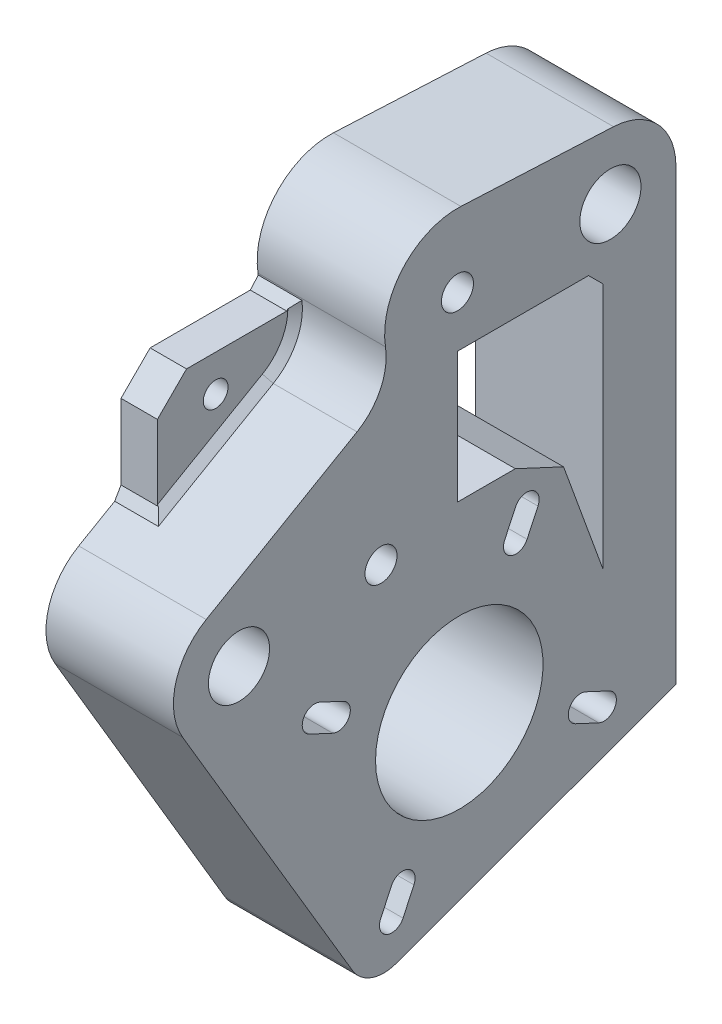
SolidWorks part; units mm, degrees
ref_plane "Front Plane" through (0, 0, 0) normal (0, 0, 1) x (1, 0, 0)
ref_plane "Top Plane" through (0, 0, 0) normal (0, 1, 0) x (1, 0, 0)
ref_plane "Right Plane" through (0, 0, 0) normal (1, 0, 0) x (0, 0, -1)
ref_plane "Plane1" through (0, 0, 0) normal (-1, 0, 0) x (0, -1, 0)
sketch "Sketch1" plane through (0, 0, 0) normal (-1, 0, 0) x (0, -1, 0)
  line L0 (11.2005, 72.3805) -> (-8.7575, 37.8123)
  line L1 (-24.9887, 29.5238) -> (-23.5812, 0)
  line L2 (-23.5812, 0) -> (46.6053, 0)
  line L3 (46.6053, 0) -> (62.0013, 42.3)
  line L4 (62.0013, 42.3) -> (11.2005, 72.3805)
  arc A0 (-8.7575, 37.8123) -> (-24.9887, 29.5238) centre (-15, 30) ccw
extrude "Boss-Extrude1" add sketch "Sketch1" against normal blind 17.5
sketch "Sketch2" plane through (0, 0, 0) normal (-1, 0, 0) x (0, -1, 0)
  line L0 (-8.7575, 37.8123) -> (3.302, 58.7)
  line L1 (3.302, 58.7) -> (-12, 58.7)
  line L2 (-12, 58.7) -> (-12, 39.5394)
  arc A0 (-12, 39.5394) -> (-8.7575, 37.8123) centre (-15, 30) cw
extrude "Boss-Extrude2" add sketch "Sketch2" against normal blind 5
sketch "Sketch3" plane through (0, 0, 0) normal (-1, 0, 0) x (0, 0, 1)
  line L0 (18.9442, -15.9372) -> (20.4384, -19.1415)
  line L1 (23.5198, -17.7046) -> (22.0256, -14.5003)
  arc A0 (20.4384, -19.1415) -> (23.5198, -17.7046) centre (21.9791, -18.423) ccw
  arc A1 (22.0256, -14.5003) -> (18.9442, -15.9372) centre (20.4849, -15.2188) ccw
extrude "Cut-Extrude1" cut sketch "Sketch3" against normal through all
sketch "Sketch4" plane through (0, 0, 0) normal (-1, 0, 0) x (0, 0, 1)
  line L0 (48.8969, -24.2807) -> (45.6927, -25.7748)
  line L1 (47.1296, -28.8563) -> (50.3338, -27.3621)
  arc A0 (50.3338, -27.3621) -> (48.8969, -24.2807) centre (49.6154, -25.8214) ccw
  arc A1 (45.6927, -25.7748) -> (47.1296, -28.8563) centre (46.4111, -27.3156) ccw
extrude "Cut-Extrude2" cut sketch "Sketch4" against normal through all
sketch "Sketch5" plane through (0, 0, 0) normal (-1, 0, 0) x (0, 0, 1)
  line L0 (35.9779, -52.466) -> (37.472, -55.6703)
  line L1 (40.5535, -54.2334) -> (39.0593, -51.0291)
  arc A0 (37.472, -55.6703) -> (40.5535, -54.2334) centre (39.0128, -54.9518) ccw
  arc A1 (39.0593, -51.0291) -> (35.9779, -52.466) centre (37.5186, -51.7476) ccw
extrude "Cut-Extrude3" cut sketch "Sketch5" against normal through all
sketch "Sketch6" plane through (0, 0, 0) normal (-1, 0, 0) x (0, 0, 1)
  line L0 (10.6007, -45.8899) -> (13.805, -44.3958)
  line L1 (12.3681, -41.3143) -> (9.1638, -42.8085)
  arc A0 (13.805, -44.3958) -> (12.3681, -41.3143) centre (13.0866, -42.855) ccw
  arc A1 (9.1638, -42.8085) -> (10.6007, -45.8899) centre (9.8823, -44.3492) ccw
extrude "Cut-Extrude4" cut sketch "Sketch6" against normal through all
sketch "Sketch7" plane through (17.5, 0, 0) normal (1, 0, 0) x (0, 0, -1)
  line L0 (-30, 8) -> (-30, -9.9381)
  line L1 (-30, -9.9381) -> (-16.5539, -9.9381)
  line L2 (-16.5539, -9.9381) -> (-10, -27.9449)
  line L3 (-10, -27.9449) -> (-10, 8)
  line L4 (-10, 8) -> (-30, 8)
extrude "Cut-Extrude5" cut sketch "Sketch7" against normal through all
hole_wizard "Hole1" positions "Sketch9" profile "Sketch8" legacy
sketch "Sketch9" plane through (5, 0, 0) normal (1, 0, 0) x (0, 0, -1)
  point P0 (-50.7, 7)
sketch "Sketch8" plane through (5, 7, 50.7) normal (0, 1, 0) x (0, 0, -1)
  line L0 (0, 0) -> (0, 5)
  line L1 (0, 5) -> (1.7, 5)
  line L2 (1.7, 5) -> (1.7, 0)
  line L3 (1.7, 0) -> (0, 0)
  line L4 (0, 110) -> (0, -10) construction
  dimension "Diameter" = 3.4
  dimension "Depth" = 5
hole_wizard "Hole2" positions "Sketch11" profile "Sketch10" legacy
sketch "Sketch11" plane through (0, 0, 0) normal (-1, 0, 0) x (0, 0, 1)
  point P0 (9, 15)
sketch "Sketch10" plane through (0, 15, 9) normal (0, 1, 0) x (0, 0, 1)
  line L0 (0, 0) -> (0, 17.5)
  line L1 (0, 17.5) -> (4.2, 17.5)
  line L2 (4.2, 17.5) -> (4.2, 0)
  line L3 (4.2, 0) -> (0, 0)
  line L4 (0, 110) -> (0, -10) construction
  dimension "Diameter" = 8.4
  dimension "Depth" = 17.5
hole_wizard "Hole3" positions "Sketch13" profile "Sketch12" legacy
sketch "Sketch13" plane through (0, 0, 0) normal (-1, 0, 0) x (0, 0, 1)
  point P0 (40.5, -12.1507)
sketch "Sketch12" plane through (0, -12.1507, 40.5) normal (0, 1, 0) x (0, 0, 1)
  line L0 (0, 0) -> (0, 17.5)
  line L1 (0, 17.5) -> (2.2, 17.5)
  line L2 (2.2, 17.5) -> (2.2, 0)
  line L3 (2.2, 0) -> (0, 0)
  line L4 (0, 110) -> (0, -10) construction
  dimension "Diameter" = 4.4
  dimension "Depth" = 17.5
hole_wizard "Hole4" positions "Sketch15" profile "Sketch14" legacy
sketch "Sketch15" plane through (0, 0, 0) normal (-1, 0, 0) x (0, 0, 1)
  point P0 (29.7488, -35.0853)
sketch "Sketch14" plane through (0, -35.0853, 29.7488) normal (0, 1, 0) x (0, 0, 1)
  line L0 (0, 0) -> (0, 17.5)
  line L1 (0, 17.5) -> (11.5, 17.5)
  line L2 (11.5, 17.5) -> (11.5, 0)
  line L3 (11.5, 0) -> (0, 0)
  line L4 (0, 110) -> (0, -10) construction
  dimension "Diameter" = 23
  dimension "Depth" = 17.5
hole_wizard "Hole5" positions "Sketch17" profile "Sketch16" legacy
sketch "Sketch17" plane through (0, 0, 0) normal (-1, 0, 0) x (0, 0, 1)
  point P0 (60, -14.4449)
sketch "Sketch16" plane through (0, -14.4449, 60) normal (0, 1, 0) x (0, 0, 1)
  line L0 (0, 0) -> (0, 17.5)
  line L1 (0, 17.5) -> (4.2, 17.5)
  line L2 (4.2, 17.5) -> (4.2, 0)
  line L3 (4.2, 0) -> (0, 0)
  line L4 (0, 110) -> (0, -10) construction
  dimension "Diameter" = 8.4
  dimension "Depth" = 17.5
hole_wizard "Hole6" positions "Sketch19" profile "Sketch18" legacy
sketch "Sketch19" plane through (0, 0, 0) normal (-1, 0, 0) x (0, 0, 1)
  point P0 (30, 15)
sketch "Sketch18" plane through (0, 15, 30) normal (0, 1, 0) x (0, 0, 1)
  line L0 (0, 0) -> (0, 17.5)
  line L1 (0, 17.5) -> (2.2, 17.5)
  line L2 (2.2, 17.5) -> (2.2, 0)
  line L3 (2.2, 0) -> (0, 0)
  line L4 (0, 110) -> (0, -10) construction
  dimension "Diameter" = 4.4
  dimension "Depth" = 17.5
fillet "Fillet1" radius 8 1 edges at (11.25, 8.7575, 37.8123) tangent propagation no
chamfer "Chamfer1" distance 3.2893 angle 45 1 edges at (8.75, -9.9381, 16.5539) first distance on face at (8.75, -18.9415, 13.277)
chamfer "Chamfer2" distance 1 angle 30 1 edges at (2.5, -3.302, 58.7) first distance on face at (7.5, -3.0647, 58.289)
chamfer "Chamfer3" distance 4 angle 45 1 edges at (2.5, 12, 58.7)
chamfer "Chamfer4" distance 2 angle 45 1 edges at (8.75, 8, 10)
chamfer "Chamfer5" distance 1.1548 angle 48.269 1 edges at (2.5, 12, 39.7901) first distance on face at (2.5, 12, 47.245)
chamfer "Chamfer6" distance 1 angle 45 2 edges at (5, 8.6749, 40.6231) (5, 0.7531, 51.6763)
fillet "Fillet2" radius 5 1 edges at (8.75, -62.0013, 42.3) tangent propagation no
fillet "Fillet3" radius 9 1 edges at (8.75, -11.2005, 72.3805) tangent propagation no
fillet "Fillet4" radius 9 1 edges at (8.75, 23.5812, 0)
